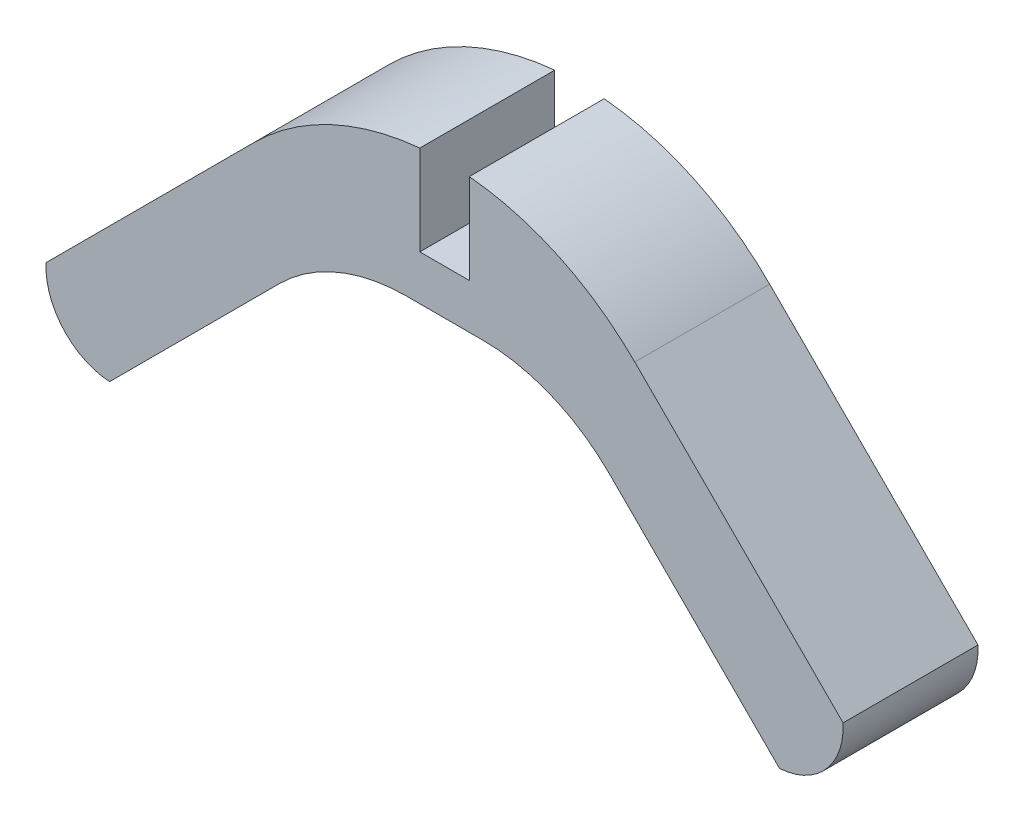
SolidWorks part; units mm, degrees
ref_plane "Front Plane" through (0, 0, 0) normal (0, 0, 1) x (1, 0, 0)
ref_plane "Top Plane" through (0, 0, 0) normal (0, 1, 0) x (1, 0, 0)
ref_plane "Right Plane" through (0, 0, 0) normal (1, 0, 0) x (0, 0, -1)
sketch "Schizzo2" plane through (0, 0, 0) normal (0, 0, 1) x (1, 0, 0)
  line L0 (12.5, 0) -> (-12.5, 0)
  line L1 (-12.5, 0) -> (-37.2487, -24.7487)
  line L5 (-44.3198, -16.8198) -> (-12.5, 15)
  line L6 (-12.5, 15) -> (-2.75, 15)
  line L7 (-2.75, 15) -> (-2.75, 5)
  line L8 (-2.75, 5) -> (2.75, 5)
  line L9 (0, 0) -> (0, 20.408) construction
  line L10 (2.75, 15) -> (2.75, 5)
  line L11 (12.5, 15) -> (2.75, 15)
  line L12 (44.3198, -16.8198) -> (12.5, 15)
  line L16 (12.5, 0) -> (37.2487, -24.7487)
  line L17 (-37.2487, -24.7487) -> (37.2487, -24.7487) construction
  line L18 (-12.5, 0) -> (-12.5, -24.7487) construction
  arc A0 (-37.2487, -24.7487) -> (-44.3198, -16.8198) centre (-36.7643, -17.1993) cw
  arc A1 (37.2487, -24.7487) -> (44.3198, -16.8198) centre (36.7643, -17.1993) ccw
  point P6 (-50.4121, -17.9121)
  point P14 (0, 5)
  point P17 (-38.732, -18.7637)
  point P18 (-38.732, -18.7637)
  point P21 (0, 0)
  dimension "D1" = 5.5
  dimension "D2" = 15
  dimension "D3" = 10
  dimension "D4" = 25
  dimension "D5" = 25
  dimension "D6" = 45
  dimension "D7" = 35
  dimension "D8" = 45
extrude "Estrusione-Estrusione1" add sketch "Schizzo2" along normal blind 15
fillet "Raccordo1" radius 30 2 edges at (12.5, 15, 7.5) (-12.5, 15, 7.5)
fillet "Raccordo2" radius 20 2 edges at (-12.5, 0, 7.5) (12.5, 0, 7.5)
